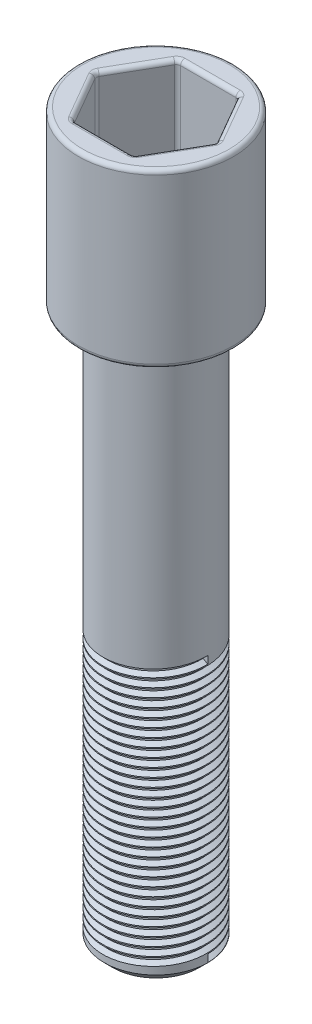
SolidWorks part; units mm, degrees
material "AISI 4140 Steel, quenched & tempered"
ref_plane "Front Plane" through (0, 0, 0) normal (1, 0, 0) x (0, 1, 0)
ref_plane "Top Plane" through (0, 0, 0) normal (0, 0, 1) x (0, 1, 0)
ref_plane "Right Plane" through (0, 0, 0) normal (0, 1, 0) x (-1, 0, 0)
sketch "Sketch1" plane through (0, 0, 0) normal (1, 0, 0) x (0, 1, 0)
  line L0 (-122.9929, 0) -> (42.9358, 0) construction
  line L1 (0, 23.268) -> (0, -20.4189) construction
  line L2 (10, 0) -> (10, 4.5)
  line L3 (10, 4.5) -> (0, 4.5)
  line L4 (0, 4.5) -> (0, 3)
  line L5 (0, 3) -> (-32, 3)
  line L6 (-32, 3) -> (-32, 0)
  line L7 (-32, 0) -> (10, 0)
  dimension "D1" = 10
  dimension "D2" = 9
  dimension "D3" = 6
  dimension "D4" = 32
revolve "Revolve1" add sketch "Sketch1" angle 360 about L0
sketch "Sketch2" plane through (0, 10, 0) normal (0, 1, 0) x (-1, 0, 0)
  line L1 (1.75, -3.0311) -> (3.5, 0)
  line L2 (3.5, 0) -> (1.75, 3.0311)
  line L3 (1.75, 3.0311) -> (-1.75, 3.0311)
  line L4 (-1.75, 3.0311) -> (-3.5, 0)
  line L5 (-3.5, 0) -> (-1.75, -3.0311)
  line L6 (-1.75, -3.0311) -> (1.75, -3.0311)
  circle A0 centre (0, 0) radius 3.0311 construction
  dimension "D1" = 3.5
extrude "Cut-Extrude1" cut sketch "Sketch2" against normal blind 8
ref_axis "Axis1" through (0, 16, 0) along (0, -1, 0)
thread "Thread2" pitch 0.5 method cut profile "Thread Profile2" start angle 0, offset 0.5, length 15, pitch 0.5, diameter 6
ref_plane "Plane2" through (3, -31.5, 0) normal (0, 0, 1) x (1, 0, 0)
sketch "Thread Profile2" plane through (3, -31.5, 0) normal (0, 0, 1) x (1, 0, 0)
  line L0 (0, 0) -> (0, 0.5) construction
  line L11 (0, 0) -> (0, 0.4375)
  line L12 (0, 0.4375) -> (-0.2706, 0.2812)
  line L13 (-0.2706, 0.2812) -> (-0.2706, 0.1562)
  line L15 (-0.2706, 0.1562) -> (0, 0)
  line L17 (-0.2706, 0.2187) -> (0, 0.2187) construction
  point P2 (0, 0)
  dimension "Pitch" = 0.5
  dimension "Profile_Angle" = 60
  dimension "Profile_Land" = 0.125
  dimension "Profile_Height" = 0.2706
chamfer "Chamfer1" distance 0.5 angle 45 1 edges at (0, -32, -3)
fillet "Fillet1" radius 0.25 20 edges at (0, 0, -4.5) (0, 10, -4.5) (0, 10, -3.0311) (-2.625, 10, -1.5155) (-2.625, 10, 1.5155) (0, 10, 3.0311) (2.625, 10, 1.5155) (2.625, 10, -1.5155) (0, 2, -3.0311) (-2.625, 2, -1.5155) (-2.625, 2, 1.5155) (0, 2, 3.0311) (2.625, 2, 1.5155) (2.625, 2, -1.5155) (-1.75, 6, -3.0311) (-1.75, 6, 3.0311) (1.75, 6, 3.0311) (3.5, 6, 0) (1.75, 6, -3.0311) (-3.5, 6, 0)
